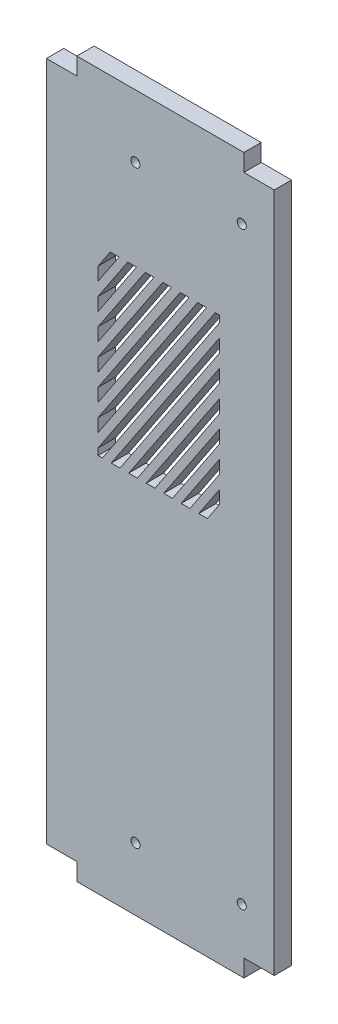
SolidWorks part; units mm, degrees
ref_plane "Front Plane" through (0, 0, 0) normal (0, 0, 1) x (1, 0, 0)
ref_plane "Top Plane" through (0, 0, 0) normal (0, 1, 0) x (1, 0, 0)
ref_plane "Right Plane" through (0, 0, 0) normal (1, 0, 0) x (0, 0, -1)
sketch "Sketch1" plane through (0, 0, 0) normal (0, 0, 1) x (1, 0, 0)
  line L1 (0, 0) -> (75, 0)
  line L2 (0, 0) -> (0, 235.4)
  line L3 (0, 235.4) -> (75, 235.4)
  line L4 (75, 0) -> (75, 235.4)
  dimension "D1" = 235.4
  dimension "D2" = 75
extrude "Boss-Extrude1" add sketch "Sketch1" along normal blind 5.7
sketch "Sketch2" plane through (0, 0, 0) normal (0, 0, -1) x (-1, 0, 0)
  line L2 (-75, 0) -> (-65, 0)
  line L3 (-75, 0) -> (-75, 5.7)
  line L4 (-75, 5.7) -> (-65, 5.7)
  line L6 (-65, 0) -> (-65, 5.7)
  line L7 (0, 0) -> (-10, 0)
  line L8 (0, 0) -> (0, 5.7)
  line L9 (0, 5.7) -> (-10, 5.7)
  line L12 (-10, 0) -> (-10, 5.7)
  line L13 (0, 235.4) -> (-10, 235.4)
  line L14 (0, 235.4) -> (0, 229.7)
  line L15 (0, 229.7) -> (-10, 229.7)
  line L16 (-10, 235.4) -> (-10, 229.7)
  line L17 (-75, 235.4) -> (-65, 235.4)
  line L18 (-75, 235.4) -> (-75, 229.7)
  line L19 (-75, 229.7) -> (-65, 229.7)
  line L20 (-65, 235.4) -> (-65, 229.7)
  dimension "D1" = 5.7
  dimension "D2" = 5.7
  dimension "D3" = 10
  dimension "D4" = 10
  dimension "D5" = 10
  dimension "D6" = 5.7
  dimension "D7" = 5.7
  dimension "D8" = 10
extrude "Cut-Extrude1" cut sketch "Sketch2" against normal blind 5.7
sketch "Sketch3" plane through (0, 0, 5.7) normal (0, 0, 1) x (1, 0, 0)
  line L1 (75, 5.7) -> (75, 229.7) construction
  line L39 (57, 185) -> (17, 125) construction
  line L40 (17, 185) -> (57, 185)
  line L41 (17, 185) -> (17, 125)
  line L42 (17, 125) -> (57, 125)
  line L43 (57, 185) -> (57, 125)
  line L44 (55.5578, 185) -> (17, 127.1633)
  line L45 (57, 182.8367) -> (18.4422, 125)
  line L46 (37, 155) -> (17, 155) construction
  line L47 (37, 155) -> (57, 155) construction
  line L48 (52.6778, 185) -> (17, 131.4833)
  line L49 (49.7978, 185) -> (17, 135.8033)
  line L50 (46.9178, 185) -> (17, 140.1233)
  line L51 (44.0378, 185) -> (17, 144.4433)
  line L52 (41.1578, 185) -> (17, 148.7633)
  line L53 (38.2778, 185) -> (17, 153.0833)
  line L54 (35.3978, 185) -> (17, 157.4033)
  line L55 (32.5178, 185) -> (17, 161.7233)
  line L56 (29.6378, 185) -> (17, 166.0433)
  line L57 (26.7578, 185) -> (17, 170.3633)
  line L58 (23.8778, 185) -> (17, 174.6833)
  line L59 (20.9978, 185) -> (17, 179.0033)
  line L60 (18.1178, 185) -> (17, 183.3233)
  line L61 (57, 178.5167) -> (21.3222, 125)
  line L62 (57, 174.1967) -> (24.2022, 125)
  line L63 (57, 169.8767) -> (27.0822, 125)
  line L64 (57, 165.5567) -> (29.9622, 125)
  line L65 (57, 161.2367) -> (32.8422, 125)
  line L66 (57, 156.9167) -> (35.7222, 125)
  line L67 (57, 152.5967) -> (38.6022, 125)
  line L68 (57, 148.2767) -> (41.4822, 125)
  line L69 (57, 143.9567) -> (44.3622, 125)
  line L70 (57, 139.6367) -> (47.2422, 125)
  line L71 (57, 135.3167) -> (50.1222, 125)
  line L72 (57, 130.9967) -> (53.0022, 125)
  line L73 (57, 126.6767) -> (55.8822, 125)
  line L74 (10, 0) -> (65, 0) construction
  point P79 (35.5578, 155)
  point P82 (38.4422, 155)
  dimension "D7" = 40
  dimension "D8" = 155
  dimension "D9" = 38
  dimension "D10" = 1.2
  dimension "D11" = 2.3963
  dimension "D12" = 2.3963
  dimension "D13" = 2.3963
  dimension "D14" = 2.3963
  dimension "D15" = 2.3963
  dimension "D16" = 2.3963
  dimension "D17" = 2.3963
  dimension "D18" = 2.3963
  dimension "D19" = 2.3963
  dimension "D20" = 2.3963
  dimension "D21" = 2.3963
  dimension "D22" = 2.3963
  dimension "D23" = 2.3963
  dimension "D24" = 2.3963
  dimension "D25" = 2.3963
  dimension "D26" = 2.3963
  dimension "D27" = 2.3963
  dimension "D28" = 2.3963
  dimension "D29" = 2.3963
  dimension "D30" = 2.3963
  dimension "D31" = 2.3963
  dimension "D32" = 2.3963
  dimension "D33" = 2.3963
  dimension "D34" = 2.3963
  dimension "D35" = 2.3963
  dimension "D36" = 2.3963
  dimension "D37" = 60
extrude "Cut-Extrude2" cut sketch "Sketch3" against normal blind 5.7 contours L45 L43 L40 L44 L41 L42 | L40 L49 L41 L48 | L40 L51 L41 L50 | L40 L53 L41 L52 | L40 L55 L41 L54 | L40 L57 L41 L56 | L40 L59 L41 L58 | L62 L43 L61 L42 | L64 L43 L63 L42 | L66 L43 L65 L42 | L68 L43 L67 L42 | L70 L43 L69 L42 | L72 L43 L71 L42 region at (19.7824, 180.8263, 5.7) region at (22.6298, 176.5554, 5.7) region at (25.4993, 172.2511, 5.7) region at (28.3741, 167.9388, 5.7) region at (31.251, 163.6235, 5.7) region at (34.129, 159.3065, 5.7) region at (37, 155, 5.7) region at (39.871, 150.6935, 5.7) region at (42.749, 146.3765, 5.7) region at (45.6259, 142.0612, 5.7) region at (48.5007, 137.7489, 5.7) region at (51.3702, 133.4446, 5.7) region at (54.2176, 129.1737, 5.7)
sketch "Sketch4" plane through (0, 0, 5.7) normal (0, 0, 1) x (1, 0, 0)
  circle A0 centre (64.3, 20.7) radius 1.5
  circle A1 centre (29.3, 20.7) radius 1.5
  circle A2 centre (64.3, 214.7) radius 1.5
  circle A3 centre (29.3, 214.7) radius 1.5
extrude "Cut-Extrude3" cut sketch "Sketch4" against normal blind 2
